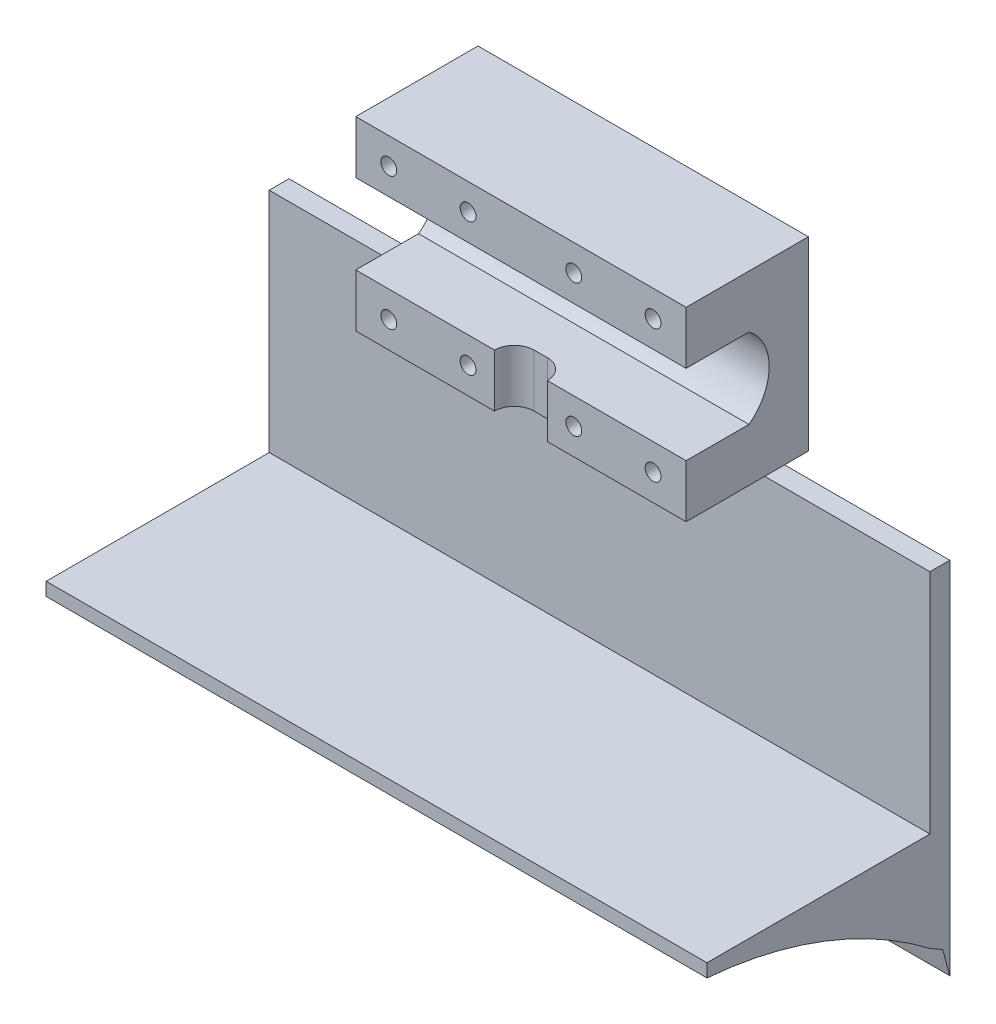
SolidWorks part; units mm, degrees
material "PLA"
ref_plane "Front Plane" through (0, 0, 0) normal (0, 0, 1) x (1, 0, 0)
ref_plane "Top Plane" through (0, 0, 0) normal (0, 1, 0) x (1, 0, 0)
ref_plane "Right Plane" through (0, 0, 0) normal (1, 0, 0) x (0, 0, -1)
sketch "Croquis1" plane through (0, 0, 0) normal (0, 0, 1) x (1, 0, 0)
  line L1 (-50, -48) -> (50, -48)
  line L2 (-50, -48) -> (-50, 19.9)
  line L3 (-25, 48) -> (25, 48)
  line L4 (50, -48) -> (50, 19.9)
  line L5 (-50, 19.9) -> (-25, 19.9)
  line L6 (-25, 19.9) -> (-25, 48)
  line L8 (50, 19.9) -> (25, 19.9)
  line L9 (25, 19.9) -> (25, 48)
  point P0 (0, 0)
  dimension "D1" = 96
  dimension "D2" = 25
  dimension "D3" = 28.1
  dimension "D4" = 25
  dimension "D5" = 50
extrude "Base" add sketch "Croquis1" along normal blind 3
sketch "Croquis2" plane through (0, 0, 3) normal (0, 0, 1) x (1, 0, 0)
  line L1 (-25, 48) -> (25, 48)
  line L2 (-25, 48) -> (-25, 19.9)
  line L3 (-25, 19.9) -> (25, 19.9)
  line L4 (25, 48) -> (25, 19.9)
extrude "Saliente-Extruir2" add sketch "Croquis2" along normal blind 15.5
sketch "Croquis3" plane through (-25, 0, 0) normal (-1, 0, 0) x (0, 0, 1)
  line L0 (18.5, 40) -> (18.5, 27.9)
  line L1 (18.5, 48) -> (18.5, 19.9) construction
  line L2 (18.5, 40) -> (9, 40)
  line L3 (18.5, 27.9) -> (9, 27.9)
  arc A2 (9, 40) -> (9, 27.9) centre (13.43, 33.95) ccw
  dimension "D3" = 7.4985
  dimension "D1" = 12.1
  dimension "D2" = 8
  dimension "D4" = 9.5
extrude "Cortar-Extruir1" cut sketch "Croquis3" against normal up to next
sketch "Croquis4" plane through (0, 19.9, 0) normal (0, -1, 0) x (1, 0, 0)
  line L1 (-25, 18.5) -> (25, 18.5) construction
  line L2 (1, 15.5) -> (-1, 15.5)
  line L3 (4, 18.5) -> (-4, 18.5)
  arc A0 (-4, 18.5) -> (-1, 15.5) centre (-1, 18.5) ccw
  arc A1 (4, 18.5) -> (1, 15.5) centre (1, 18.5) cw
  point P0 (0, 18.5)
  point P1 (0, 15.5)
  dimension "D1" = 4
  dimension "D4" = 3
  dimension "D2" = 3
  dimension "D3" = 1
extrude "Cortar-Extruir2" cut sketch "Croquis4" against normal up to next
sketch "Croquis5" plane through (0, 0, 18.5) normal (0, 0, 1) x (1, 0, 0)
  circle A0 centre (-20, 44) radius 1.2
  circle A1 centre (-8, 44) radius 1.2
  circle A2 centre (-20, 23.9) radius 1.2
  circle A3 centre (-8, 23.9) radius 1.2
  circle A4 centre (8, 44) radius 1.2
  circle A5 centre (20, 44) radius 1.2
  circle A6 centre (8, 23.9) radius 1.2
  circle A7 centre (20, 23.9) radius 1.2
  point P2 (-8, 44)
  point P3 (-8, 23.9)
  point P4 (-20, 23.9)
  point P5 (-20, 44)
  point P10 (20, 44)
  point P11 (20, 23.9)
  point P12 (8, 23.9)
  point P13 (8, 44)
  dimension "D1" = 2
  dimension "D2" = 2
sketch "Croquis15" plane through (0, 0, 3) normal (0, 0, 1) x (1, 0, 0)
  line L1 (-50, 19.9) -> (50, 19.9)
  line L2 (-50, 19.9) -> (-50, -34.56)
  line L3 (-50, -34.56) -> (50, -34.56)
  line L4 (50, 19.9) -> (50, -34.56)
  dimension "D1" = 100
extrude "Saliente-Extruir3" add sketch "Croquis15" along normal blind 3.6
sketch "Croquis16" plane through (0, 0, 0) normal (0, 0, -1) x (-1, 0, 0)
  line L0 (25, 19.9) -> (50, 19.9)
  line L1 (-50, 19.9) -> (-25, 19.9)
  line L2 (-50, 19.9) -> (-50, -48)
  line L3 (-50, -48) -> (50, -48)
  line L4 (50, 19.9) -> (50, -48)
  line L9 (-25, 19.9) -> (25, 19.9)
extrude "Cortar-Extruir3" cut sketch "Croquis16" against normal blind 3.6
extrude "Cortar-Extruir4" cut sketch "Croquis5" against normal blind 4
sketch "Croquis22" plane through (-50, 0, 0) normal (-1, 0, 0) x (0, 0, 1)
  line L1 (4.66, -30.6) -> (6.6, -29.4799)
  line L5 (6.6, 19.9) -> (6.6, -34.56) construction
  line L7 (6.6, -34.56) -> (3.6, -34.56)
  line L8 (4.66, -30.6) -> (3.6, -34.56)
  line L9 (6.6, -29.4799) -> (6.6, -34.56)
  dimension "D2" = 3.96
  dimension "D3" = 3
extrude "Cortar-Extruir7" cut sketch "Croquis22" against normal through all
sketch "Croquis24" plane through (-50, 0, 0) normal (-1, 0, 0) x (0, 0, 1)
  line L11 (6.6, -14.4799) -> (6.6, -29.4799)
  line L18 (6.6, -14.4799) -> (40.3453, -14.4799)
  line L21 (40.3453, -16.4799) -> (40.3453, -14.4799)
  arc A1 (6.6, -29.4799) -> (40.3453, -16.4799) centre (45.6277, -80.4899) cw
  dimension "D3" = 33.7453
  dimension "D1" = 2
  dimension "D2" = 15
extrude "Saliente-Extruir5" add sketch "Croquis24" against normal through all
